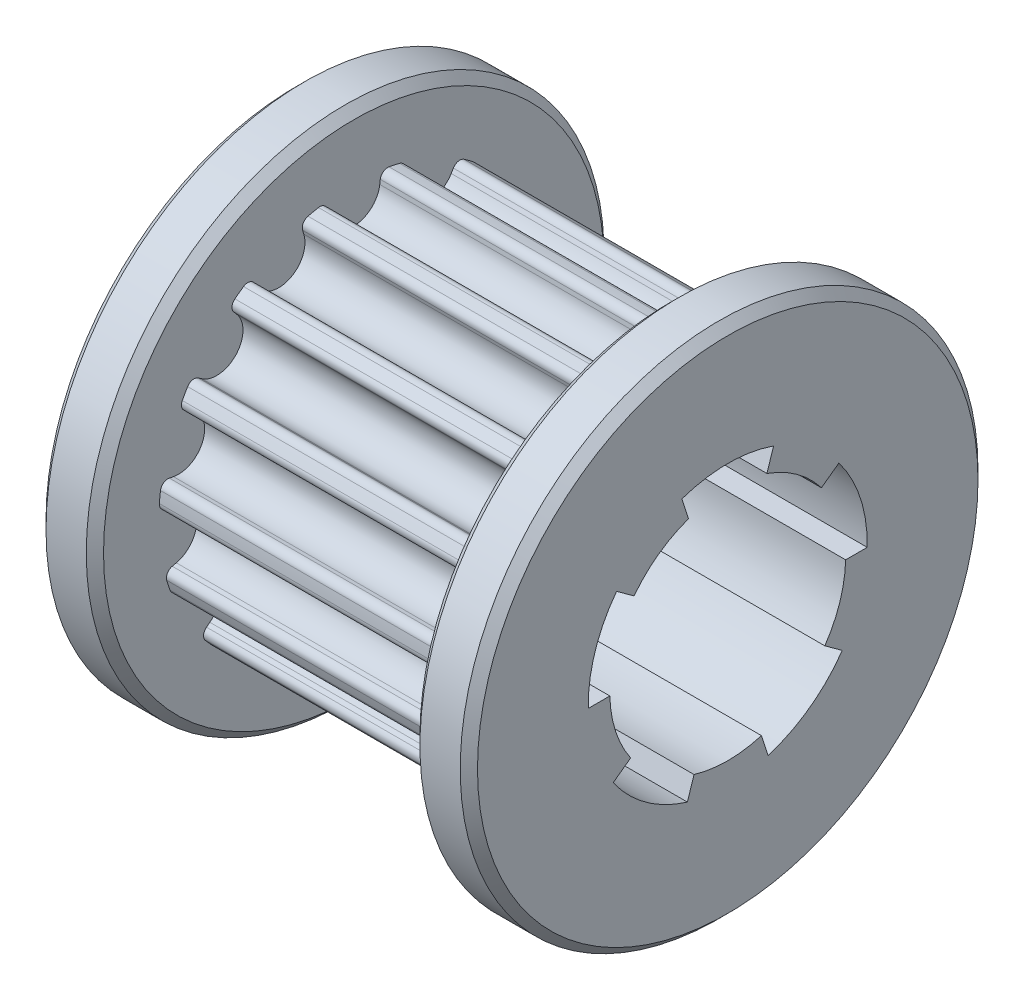
SolidWorks part; units mm, degrees
ref_plane "前视基准面" through (0, 0, 0) normal (0, 0, 1) x (1, 0, 0)
ref_plane "上视基准面" through (0, 0, 0) normal (0, 1, 0) x (1, 0, 0)
ref_plane "右视基准面" through (0, 0, 0) normal (1, 0, 0) x (0, 0, -1)
sketch "草图1" plane through (0, 0, 0) normal (0, 0, 1) x (1, 0, 0)
  line L0 (0, 0) -> (64.8368, 0) construction
  line L1 (0, 1.3558) -> (0, 6.779)
  line L2 (0, 6.779) -> (11, 6.779)
  line L3 (11, 6.779) -> (11, 2.7116)
  line L4 (11, 2.7116) -> (20, 2.7116)
  line L5 (20, 2.7116) -> (20, 1.3558)
  line L6 (20, 1.3558) -> (0, 1.3558)
  dimension "L" = 20
  dimension "B" = 11
  dimension "d" = 2.7116
  dimension "d1" = 5.4232
  dimension "da" = 13.558
revolve "旋转1" add sketch "草图1" angle 360 about L0
chamfer "倒角1" distance 1 angle 45 2 edges at (20, 0, 1.3558) (0, 0, 1.3558)
sketch "草图4" plane through (0, 0, 0) normal (-1, 0, 0) x (0, 0, 1)
  line L1 (-1, 0.9155) -> (1, 0.9155)
  line L2 (-1, 0.9155) -> (-1, 2.3558)
  line L3 (-1, 2.3558) -> (1, 2.3558)
  line L4 (1, 0.9155) -> (1, 2.3558)
  circle A0 centre (0, 0) radius 1.3558 construction
  point P6 (0, 2.3558)
  dimension "键槽高度" = 2.3558
  dimension "键槽宽度" = 2
  dimension "t1" = 1
extrude "切除-拉伸1" cut sketch "草图4" against normal through all
sketch "草图6" plane through (0, 0, 0) normal (1, 0, 0) x (0, 0, -1)
  line L0 (0, 0) -> (0, 30.6512) construction
  line L1 (0.921, 6.4432) -> (0.9032, 6.2981)
  line L2 (1.4809, 6.6153) -> (1.6775, 8.2168)
  line L3 (-1.4809, 6.6153) -> (-1.6775, 8.2168)
  line L4 (-0.921, 6.4432) -> (-0.9032, 6.2981)
  circle A0 centre (0, 0) radius 6.779 construction
  circle A1 centre (0, 0) radius 5.499 construction
  arc A2 (-0.9032, 6.2981) -> (0.9032, 6.2981) centre (0, 6.409) ccw
  arc A3 (1.6775, 8.2168) -> (-1.6775, 8.2168) centre (0, 0) ccw
  arc A4 (0.921, 6.4432) -> (1.2261, 6.6672) centre (1.1791, 6.4115) cw
  arc A5 (1.2261, 6.6672) -> (1.4809, 6.6153) centre (0, 0) cw
  arc A6 (-1.2261, 6.6672) -> (-1.4809, 6.6153) centre (0, 0) ccw
  arc A7 (-0.921, 6.4432) -> (-1.2261, 6.6672) centre (-1.1791, 6.4115) ccw
  point P7 (0, 1.9)
  point P8 (0, 29.3712)
  point P15 (0.954, 6.7115)
  dimension "D1" = 10.998
  dimension "ra" = 0.26
  dimension "rf" = 0.91
  dimension "hg" = 1.28
  dimension "D3" = 0.26
  dimension "D4" = 1.6136
  dimension "angle" = 14
  dimension "bw" = 1.9
extrude "切除-拉伸2" cut sketch "草图6" along normal up to next
ref_axis "基准轴1" through (-2.75, 0, 0) along (1, 0, 0)
pattern_circular "阵列(圆周)3" count 15 over 360 about axis through (-2.75, 0, 0) along (1, 0, 0) of "切除-拉伸2"
sketch "草图7" plane through (0, 0, 0) normal (-1, 0, 0) x (0, 0, 1)
  circle A0 centre (0, 0) radius 3
  dimension "D1" = 6
extrude "切除-拉伸3" cut sketch "草图7" against normal through all
sketch "草图9" plane through (0, 0, 0) normal (-1, 0, 0) x (0, 0, 1)
  circle A0 centre (0, 0) radius 9
  circle A1 centre (0, 0) radius 3 construction
  circle A2 centre (0, 0) radius 3
  dimension "D1" = 18
extrude "凸台-拉伸1" add sketch "草图9" along normal blind 2
sketch "草图10" plane through (11, 0, 0) normal (1, 0, 0) x (0, 0, -1)
  circle A0 centre (0, 0) radius 9
  circle A1 centre (0, 0) radius 9 construction
  circle A2 centre (0, 0) radius 3 construction
  circle A3 centre (0, 0) radius 3
extrude "凸台-拉伸2" add sketch "草图10" along normal blind 2
chamfer "倒角2" distance 0.3 angle 45 4 edges at (13, 0, -9) (11, 0, -9) (0, 0, 9) (-2, 0, 9)
sketch "草图11" plane through (-2, 0, 0) normal (-1, 0, 0) x (0, 0, 1)
  circle A1 centre (0, 0) radius 4
  dimension "D1" = 8
extrude "切除-拉伸4" cut sketch "草图11" against normal through all
sketch "草图12" plane through (-2, 0, 0) normal (-1, 0, 0) x (0, 0, 1)
  line L0 (-1.4678, 4.5175) -> (-1.2361, 3.8042)
  line L1 (1.4678, 4.5175) -> (1.2361, 3.8042)
  arc A0 (1.4678, 4.5175) -> (-1.4678, 4.5175) centre (0, 0) ccw
  circle A1 centre (0, 0) radius 4 construction
  arc A2 (1.2361, 3.8042) -> (-1.2361, 3.8042) centre (0, 0) ccw
  dimension "D1" = 9.5
  dimension "D2" = 36
extrude "切除-拉伸5" cut sketch "草图12" against normal through all
pattern_circular "阵列(圆周)4" count 5 over 360 about axis through (-2, 0, 0) along (-1, 0, 0) of "切除-拉伸5"
sketch "草图13" plane through (-2, 0, 0) normal (-1, 0, 0) x (0, 0, 1)
  line L20 (-1.5935, 4.5807) -> (-1.3617, 3.8673)
  line L21 (1.3617, 3.8673) -> (1.5935, 4.5807)
  line L22 (3.8641, 2.9311) -> (3.2572, 2.4901)
  line L23 (4.0988, -0.1) -> (4.849, -0.1)
  line L24 (3.9817, -2.7693) -> (3.3748, -2.3283)
  line L25 (1.1715, -3.9291) -> (1.4033, -4.6425)
  line L26 (-1.4033, -4.6425) -> (-1.1715, -3.9291)
  line L27 (-3.3748, -2.3283) -> (-3.9817, -2.7693)
  line L28 (-4.849, -0.1) -> (-4.0988, -0.1)
  line L29 (-3.2572, 2.4901) -> (-3.8641, 2.9311)
  line L30 (-1.5935, 4.5807) -> (-1.3617, 3.8673)
  line L31 (1.3617, 3.8673) -> (1.5935, 4.5807)
  line L32 (3.8641, 2.9311) -> (3.2572, 2.4901)
  line L33 (4.0988, -0.1) -> (4.849, -0.1)
  line L34 (3.9817, -2.7693) -> (3.3748, -2.3283)
  line L35 (1.1715, -3.9291) -> (1.4033, -4.6425)
  line L36 (-1.4033, -4.6425) -> (-1.1715, -3.9291)
  line L37 (-3.3748, -2.3283) -> (-3.9817, -2.7693)
  line L38 (-4.849, -0.1) -> (-4.0988, -0.1)
  line L39 (-3.2572, 2.4901) -> (-3.8641, 2.9311)
  arc A20 (1.5935, 4.5807) -> (-1.5935, 4.5807) centre (0, 0) ccw
  arc A21 (3.2572, 2.4901) -> (1.3617, 3.8673) centre (0, 0) ccw
  arc A22 (4.849, -0.1) -> (3.8641, 2.9311) centre (0, 0) ccw
  arc A23 (3.3748, -2.3283) -> (4.0988, -0.1) centre (0, 0) ccw
  arc A24 (1.4033, -4.6425) -> (3.9817, -2.7693) centre (0, 0) ccw
  arc A25 (-1.1715, -3.9291) -> (1.1715, -3.9291) centre (0, 0) ccw
  arc A26 (-3.9817, -2.7693) -> (-1.4033, -4.6425) centre (0, 0) ccw
  arc A27 (-4.0988, -0.1) -> (-3.3748, -2.3283) centre (0, 0) ccw
  arc A28 (-3.8641, 2.9311) -> (-4.849, -0.1) centre (0, 0) ccw
  arc A29 (-1.3617, 3.8673) -> (-3.2572, 2.4901) centre (0, 0) ccw
  arc A30 (1.5935, 4.5807) -> (-1.5935, 4.5807) centre (0, 0) ccw
  arc A31 (3.2572, 2.4901) -> (1.3617, 3.8673) centre (0, 0) ccw
  arc A32 (4.849, -0.1) -> (3.8641, 2.9311) centre (0, 0) ccw
  arc A33 (3.3748, -2.3283) -> (4.0988, -0.1) centre (0, 0) ccw
  arc A34 (1.4033, -4.6425) -> (3.9817, -2.7693) centre (0, 0) ccw
  arc A35 (-1.1715, -3.9291) -> (1.1715, -3.9291) centre (0, 0) ccw
  arc A36 (-3.9817, -2.7693) -> (-1.4033, -4.6425) centre (0, 0) ccw
  arc A37 (-4.0988, -0.1) -> (-3.3748, -2.3283) centre (0, 0) ccw
  arc A38 (-3.8641, 2.9311) -> (-4.849, -0.1) centre (0, 0) ccw
  arc A39 (-1.3617, 3.8673) -> (-3.2572, 2.4901) centre (0, 0) ccw
  dimension "D1" = 0.1
extrude "切除-拉伸6" cut sketch "草图13" against normal through all
equation "\"键槽高度@草图4\" = \"d@草图1\" / 2  + \"t1@草图4\""
equation "\"D1@草图6\" = \"da@草图1\"  - \"hg@草图6\" - \"hg@草图6\""
equation "\"D3@草图6\" = \"ra@草图6\""
